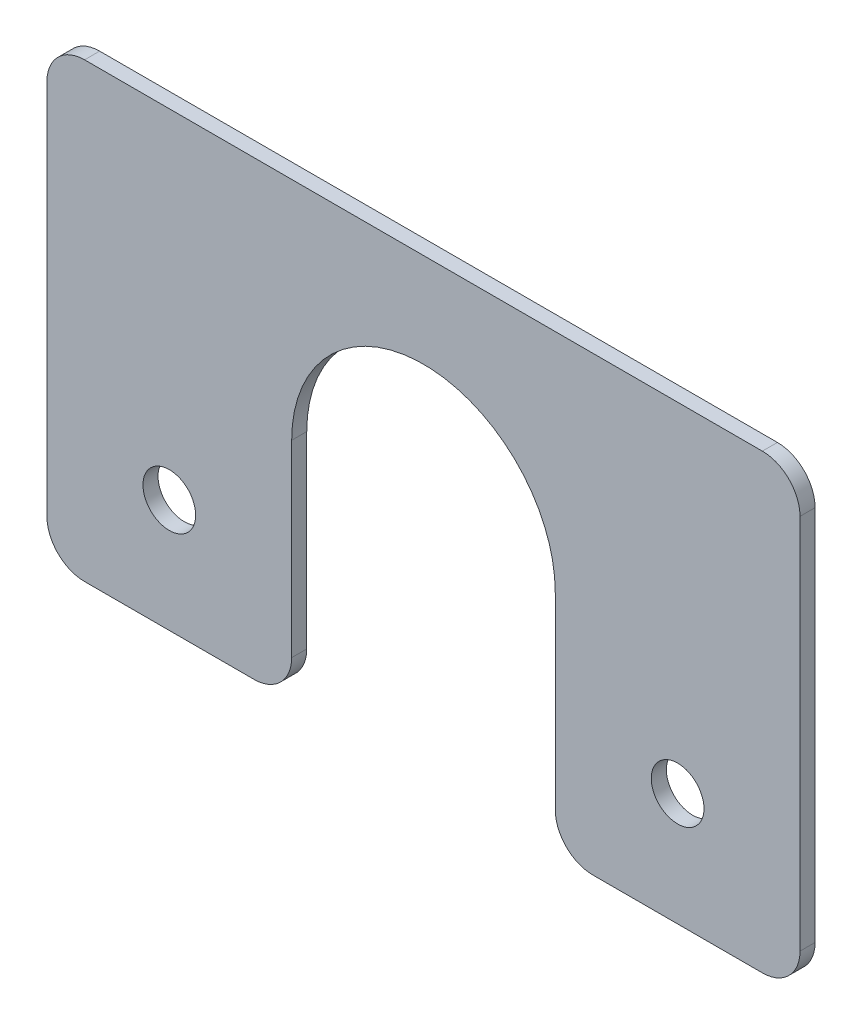
SolidWorks part; units mm, degrees
ref_plane "Front Plane" through (0, 0, 0) normal (0, 0, 1) x (1, 0, 0)
ref_plane "Top Plane" through (0, 0, 0) normal (0, 1, 0) x (1, 0, 0)
ref_plane "Right Plane" through (0, 0, 0) normal (1, 0, 0) x (0, 0, -1)
sketch "Sketch1" plane through (0, 0, 0) normal (0, 0, 1) x (1, 0, 0)
  line L1 (-50, -30) -> (50, -30)
  line L2 (-50, -30) -> (-50, 30)
  line L3 (-50, 30) -> (50, 30)
  line L4 (50, -30) -> (50, 30)
  line L5 (-50, -30) -> (50, 30) construction
  line L6 (-50, 30) -> (50, -30) construction
  point P0 (0, 0)
  dimension "D1" = 100
  dimension "D2" = 60
base flange "Base-Flange1" sketch "Sketch1" thickness 2 reverse thickness direction no parameters "D1"=2
sketch "Sketch6" plane through (0, 0, 0) normal (0, 0, 1) x (1, 0, 0)
  line L0 (-17.5, 0) -> (-17.5, -30)
  line L1 (-50, -30) -> (50, -30) construction
  line L2 (-17.5, -30) -> (17.5, -30)
  line L3 (17.5, -30) -> (17.5, 0)
  arc A0 (17.5, 0) -> (-17.5, 0) centre (0, 0) ccw
  dimension "D1" = 35
extrude "Cut-Extrude1" cut sketch "Sketch6" against normal blind 10 normal cut yes
fillet "Fillet1" radius 5 5 edges at (50, -30, -1) (50, 30, -1) (17.5, -30, -1) (-50, -30, -1) (-50, 30, -1)
sketch "Sketch7" plane through (0, 0, 0) normal (0, 0, 1) x (1, 0, 0)
  line L0 (22.5, -30) -> (45, -30) construction
  line L1 (-45, -30) -> (-17.5, -30) construction
  line L3 (-50, 25) -> (-50, -25) construction
  circle A0 centre (-33.75, -15) radius 3.5
  circle A1 centre (33.75, -15) radius 3.5
  point P4 (0, 0)
  point P7 (0, 0)
  point P8 (0, 0)
  point P9 (0, 0)
  point P12 (33.75, -30)
  dimension "D1" = 7
  dimension "D2" = 15
  dimension "D3" = 16.25
extrude "Cut-Extrude2" cut sketch "Sketch7" against normal blind 10 normal cut yes
fillet "Fillet2" radius 5 1 edges at (-17.5, -30, -1)
sketch "Bend-Lines1" [suppressed] plane through (0, 0, 0) normal (0, 1, 0) x (1, 0, 0)
sketch "Bounding-Box1" [suppressed] plane through (0, 0, 0) normal (0, 1, 0) x (1, 0, 0)
sheet metal parameters "Sheet-Metal1" thickness 2 parameters "D1"=2
flat pattern "Flat-Pattern1" [suppressed]
sketch "Bend-Lines2" plane through (0, 0, 0) normal (0, 1, 0) x (1, 0, 0)
sketch3d "Bounding-Box2" [suppressed]
  line L0 (50, -30, 0) -> (-50, -30, 0) construction
  line L1 (50, 30, 0) -> (-50, 30, 0) construction
  line L2 (50, -30, 0) -> (50, 30, 0) construction
  line L3 (-50, -30, 0) -> (-50, 30, 0) construction
sheet metal parameters "Sheet-Metal2" thickness 2 parameters "D1"=2
flat pattern "Flat-Pattern1"
sketch "Bend-Lines2" plane through (0, 0, 0) normal (0, 1, 0) x (1, 0, 0)
sketch3d "Bounding-Box2" [suppressed]
  line L0 (-50, 30, 0) -> (50, 30, 0) construction
  line L1 (-50, -30, 0) -> (50, -30, 0) construction
  line L2 (-50, 30, 0) -> (-50, -30, 0) construction
  line L3 (50, 30, 0) -> (50, -30, 0) construction
sheet metal parameters "Sheet-Metal3" thickness 2 parameters "D1"=2
flat pattern "Flat-Pattern1"
sketch "Bend-Lines2" plane through (0, 0, 0) normal (0, 1, 0) x (1, 0, 0)
sketch3d "Bounding-Box2" [suppressed]
  line L0 (-50, 30, 0) -> (50, 30, 0) construction
  line L1 (-50, -30, 0) -> (50, -30, 0) construction
  line L2 (-50, 30, 0) -> (-50, -30, 0) construction
  line L3 (50, 30, 0) -> (50, -30, 0) construction
